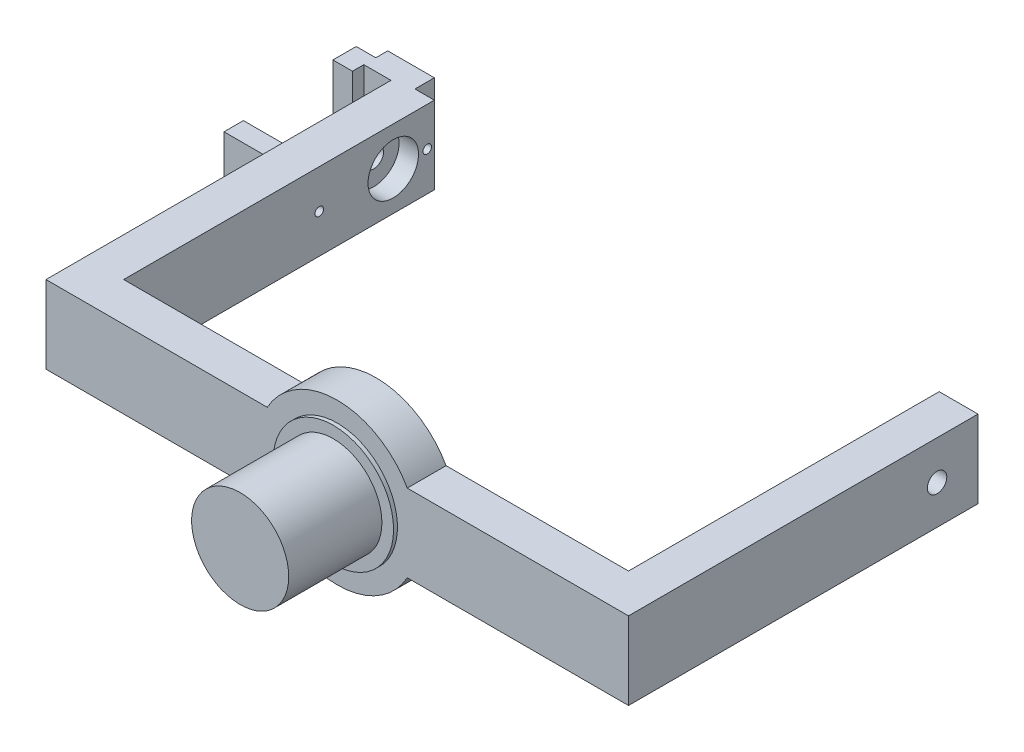
SolidWorks part; units mm, degrees
ref_plane "Płaszczyzna przednia" through (0, 0, 0) normal (0, 0, 1) x (1, 0, 0)
ref_plane "Płaszczyzna górna" through (0, 0, 0) normal (0, 1, 0) x (1, 0, 0)
ref_plane "Płaszczyzna prawa" through (0, 0, 0) normal (1, 0, 0) x (0, 0, -1)
sketch "Szkic1" plane through (0, 0, 0) normal (0, 0, 1) x (1, 0, 0)
  line L1 (-75, -10) -> (75, -10)
  line L2 (-75, -10) -> (-75, 10)
  line L3 (-75, 10) -> (75, 10)
  line L4 (75, -10) -> (75, 10)
  line L5 (-75, -10) -> (75, 10) construction
  line L6 (-75, 10) -> (75, -10) construction
  point P0 (0, 0)
  dimension "D1" = 150
  dimension "D2" = 20
extrude "Dodanie-wyciągnięcie1" add sketch "Szkic1" along normal blind 10
sketch "Szkic2" plane through (0, 0, 10) normal (0, 0, 1) x (1, 0, 0)
  circle A0 centre (0, 0) radius 20.6112
extrude "Dodanie-wyciągnięcie2" add sketch "Szkic2" against normal blind 10
sketch "Szkic3" plane through (0, 0, 10) normal (0, 0, 1) x (1, 0, 0)
  circle A0 centre (0, 0) radius 12.5
  dimension "D1" = 25
sketch "Szkic4" plane through (0, 0, 0) normal (0, 0, -1) x (-1, 0, 0)
  line L0 (18.0228, 10) -> (75, 10) construction
  line L1 (75, -10) -> (65, -10)
  line L2 (75, -10) -> (75, 10)
  line L3 (75, 10) -> (65, 10)
  line L4 (65, -10) -> (65, 10)
  dimension "D1" = 10
extrude "Dodanie-wyciągnięcie3" add sketch "Szkic4" along normal blind 80
sketch "Szkic5" plane through (-65, 0, 0) normal (1, 0, 0) x (0, 0, -1)
  circle A0 centre (69.42, 0) radius 6.5
  dimension "D1" = 13
extrude "Wytnij-wyciągnięcie2" cut sketch "Szkic5" against normal blind 5
sketch "Szkic6" plane through (0, 0, 0) normal (0, 0, -1) x (-1, 0, 0)
  line L0 (-75, 10) -> (-18.0228, 10) construction
  line L1 (-75, -10) -> (-65, -10)
  line L2 (-75, -10) -> (-75, 10)
  line L3 (-75, 10) -> (-65, 10)
  line L4 (-65, -10) -> (-65, 10)
  dimension "D1" = 10
extrude "Dodanie-wyciągnięcie4" add sketch "Szkic6" along normal blind 80
sketch "Szkic7" plane through (65, 0, 0) normal (-1, 0, 0) x (0, 0, 1)
  circle A0 centre (-69.4591, 0) radius 6.5
  dimension "D1" = 13
extrude "Wytnij-wyciągnięcie3" cut sketch "Szkic7" against normal blind 5
extrude "Dodanie-wyciągnięcie5" add sketch "Szkic3" along normal blind 25 contours A0
sketch "Szkic8" plane through (0, 0, 10) normal (0, 0, 1) x (1, 0, 0)
  circle A0 centre (0, 0) radius 15.5
  dimension "D1" = 31
extrude "Dodanie-wyciągnięcie6" add sketch "Szkic8" along normal blind 1
sketch "Szkic9" plane through (70, 0, 0) normal (-1, 0, 0) x (0, 0, 1)
  circle A0 centre (-69.4591, 0) radius 2.5
extrude "Wytnij-wyciągnięcie4" cut sketch "Szkic9" against normal blind 10
sketch "Szkic10" plane through (-70, 0, 0) normal (1, 0, 0) x (0, 0, -1)
  circle A0 centre (69.42, 0) radius 2.5
extrude "Wytnij-wyciągnięcie5" cut sketch "Szkic10" against normal blind 10
sketch "Szkic14" plane through (-75, 0, 0) normal (-1, 0, 0) x (0, 0, 1)
  circle A0 centre (-50.37, 0) radius 1.1
  circle A1 centre (-78.17, 0) radius 1.1
extrude "Wytnij-wyciągnięcie8" cut sketch "Szkic14" against normal blind 10
sketch "Szkic15" plane through (-75, 0, 0) normal (-1, 0, 0) x (0, 0, 1)
  line L1 (-52.87, -8) -> (-47.87, -8)
  line L2 (-52.87, -8) -> (-52.87, 8)
  line L3 (-52.87, 8) -> (-47.87, 8)
  line L4 (-47.87, -8) -> (-47.87, 8)
  line L5 (-52.87, -8) -> (-47.87, 8) construction
  line L6 (-52.87, 8) -> (-47.87, -8) construction
  point P0 (-50.37, 0)
  dimension "D1" = 16
  dimension "D2" = 5
extrude "Dodanie-wyciągnięcie7" add sketch "Szkic15" along normal up to surface (12.033 mm away)
sketch "Szkic16" plane through (0, 0, -80) normal (0, 0, -1) x (-1, 0, 0)
  line L0 (65, -10) -> (75, -10) construction
  line L1 (70, -10) -> (75, -10)
  line L2 (70, -10) -> (70, 10)
  line L3 (70, 10) -> (75, 10)
  line L4 (75, -10) -> (75, 10)
extrude "Dodanie-wyciągnięcie8" add sketch "Szkic16" along normal blind 5
sketch "Szkic17" plane through (-75, 0, 0) normal (-1, 0, 0) x (0, 0, 1)
  line L0 (10, 10) -> (-85, 10) construction
  line L1 (-85, -10) -> (-78.8442, -10)
  line L2 (-85, -10) -> (-85, 10)
  line L3 (-85, 10) -> (-78.8442, 10)
  line L4 (-78.8442, -10) -> (-78.8442, 10)
extrude "Dodanie-wyciągnięcie9" add sketch "Szkic17" along normal blind 7
sketch "Szkic18" plane through (-82, 0, 0) normal (-1, 0, 0) x (0, 0, 1)
  line L0 (-85, -10) -> (-78.8442, -10) construction
  line L1 (-81.9221, -10) -> (-75.9221, -10)
  line L2 (-81.9221, -10) -> (-81.9221, 10)
  line L3 (-81.9221, 10) -> (-75.9221, 10)
  line L4 (-75.9221, -10) -> (-75.9221, 10)
  dimension "D1" = 6
extrude "Dodanie-wyciągnięcie10" add sketch "Szkic18" along normal up to surface (5.033 mm away)
